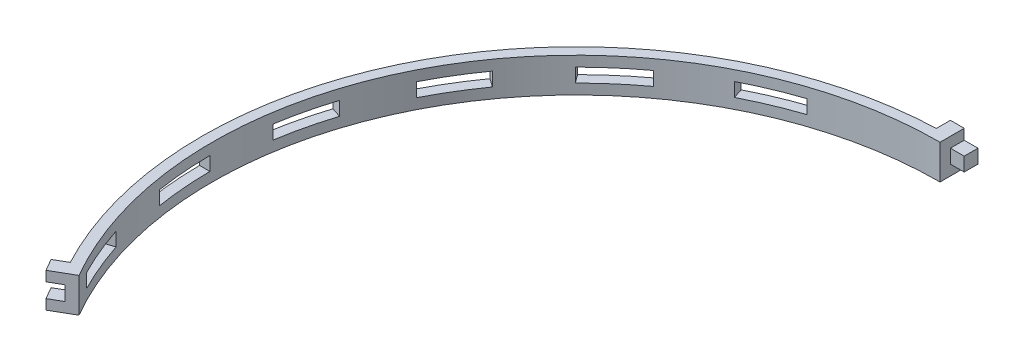
SolidWorks part; units mm, degrees
note: '?' marks a value the reader was unsure of.
ref_plane "Front Plane" through (0, 0, 0) normal (0, 0, 1) x (1, 0, 0)
ref_plane "Top Plane" through (0, 0, 0) normal (0, 1, 0) x (1, 0, 0)
ref_plane "Right Plane" through (0, 0, 0) normal (1, 0, 0) x (0, 0, -1)
sketch "Sketch1" plane through (0, 0, 0) normal (0, 1, 0) x (1, 0, 0)
  line L0 (108.5, 0) -> (105.5, 0) construction
  line L1 (0, 108.5) -> (0, -108.5)
  line L6 (0, 0) -> (-215.0076, 0) construction
  line L7 (0, 0) -> (-93.9638, -54.25)
  line L17 (0, 108.5) -> (0, 105.5)
  line L18 (0, 106) -> (-4, 106)
  line L19 (0, 106) -> (0, 112.5)
  line L20 (0, 112.5) -> (-4, 112.5)
  line L21 (-4, 106) -> (-4, 112.5)
  line L22 (-91.7987, -53) -> (-97.4279, -56.25)
  line L23 (-97.4279, -56.25) -> (-99.4279, -52.7859)
  line L24 (-99.4279, -52.7859) -> (-93.7987, -49.5359)
  line L25 (-93.7987, -49.5359) -> (-91.7987, -53)
  circle A0 centre (0, 0) radius 105.5
  circle A1 centre (0, 0) radius 108.5
  dimension "D1" = 211
  dimension "D2" = 3
  dimension "D3" = 120
  dimension "D4" = 4
  dimension "D5" = 4
  dimension "D6" = 4
  dimension "D7" = 4
  dimension "D8" = 106
  dimension "D9" = 106
extrude "Boss-Extrude1" add sketch "Sketch1" along normal blind 10
ref_axis "Axis1" through (0, 10, 0) along (0, -1, 0)?
sketch "Sketch2" plane through (-97.4279, 0, 56.25) normal (-0.866, 0, 0.5) x (0.5, 0, 0.866)
  line L1 (-4, 7.1) -> (4, 7.1)
  line L2 (-4, 7.1) -> (-4, 2.9)
  line L3 (-4, 2.9) -> (4, 2.9)
  line L4 (4, 7.1) -> (4, 2.9)
  line L5 (-4, 10) -> (-4, 0) construction
  point P6 (-4, 5)
  point P7 (-4, 5)
  dimension "D1" = 4.2
  dimension "D2" = 8
extrude "Cut-Extrude1" cut sketch "Sketch2" against normal blind 4
sketch "Sketch3" plane through (0, 0, -112.5) normal (0, 0, -1) x (-1, 0, 0)
  line L1 (4, 3) -> (-4, 3)
  line L2 (4, 3) -> (4, 7)
  line L3 (4, 7) -> (-4, 7)
  line L4 (-4, 3) -> (-4, 7)
  line L5 (4, 10) -> (4, 0) construction
  point P6 (4, 5)
  point P7 (4, 5)
  dimension "D2" = 8
  dimension "D1" = 4
extrude "Boss-Extrude2" add sketch "Sketch3" against normal blind 4 contours L2 L1 L4 L3
sketch "Sketch4" plane through (0, 0, 0) normal (1, 0, 0) x (0, 0, -1)
  line L0 (-50.749, 0) -> (108.4262, 0) construction
  line L1 (-0.6723, 7) -> (-16.6723, 7)
  line L2 (-0.6723, 7) -> (-0.6723, 3)
  line L3 (-0.6723, 3) -> (-16.6723, 3)
  line L4 (-16.6723, 7) -> (-16.6723, 3)
  line L5 (108.4262, 10) -> (-50.749, 10) construction
  dimension "D1" = 3
  dimension "D2" = 3
  dimension "D3" = 16
extrude "Cut-Extrude2" cut sketch "Sketch4" against normal through all
pattern_circular "CirPattern4" count 5 every 18 about axis through (0, 0, 0) along (0, 1, 0) of "Cut-Extrude2"
equation "\"key_height\"= 4mm"
equation "\"slot_height\"= \"key_height\" + 0.2mm"
equation "\"D1@Sketch2\"=\"slot_height\""
equation "\"D1@Sketch3\"=\"key_height\""
